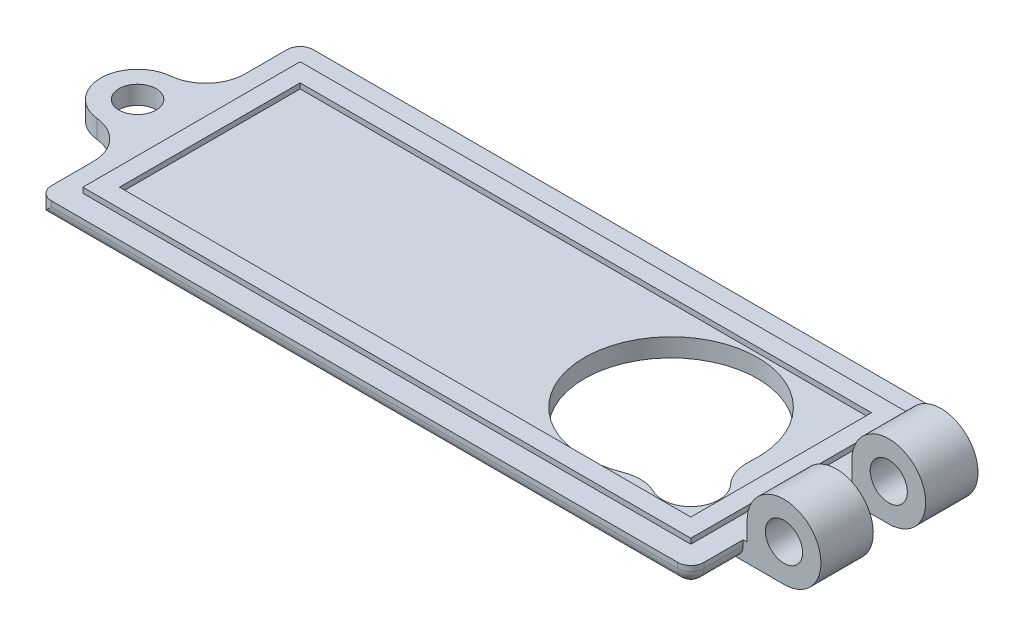
SolidWorks part; units mm, degrees
ref_plane "Front Plane" through (0, 0, 0) normal (0, 0, 1) x (1, 0, 0)
ref_plane "Top Plane" through (0, 0, 0) normal (0, 1, 0) x (1, 0, 0)
ref_plane "Right Plane" through (0, 0, 0) normal (1, 0, 0) x (0, 0, -1)
sketch "Sketch1" plane through (0, 0, 0) normal (0, 1, 0) x (1, 0, 0)
  line L1 (0, 0) -> (63.2968, 0)
  line L2 (0, 0) -> (0, 25.4)
  line L3 (0, 25.4) -> (63.2968, 25.4)
  line L4 (63.2968, 0) -> (63.2968, 25.4)
  dimension "D1" = 25.4
  dimension "D2" = 63.2968
extrude "Boss-Extrude1" add sketch "Sketch1" along normal blind 1.778
sketch "Sketch2" plane through (0, 1.778, 0) normal (0, 1, 0) x (1, 0, 0)
  line L4 (59.3598, 21.463) -> (3.937, 21.463)
  line L5 (3.937, 21.463) -> (3.937, 3.937)
  line L6 (3.937, 3.937) -> (59.3598, 3.937)
  line L7 (59.3598, 3.937) -> (59.3598, 21.463)
  line L8 (2.159, 23.241) -> (2.159, 2.159)
  line L9 (2.159, 2.159) -> (61.1378, 2.159)
  line L10 (61.1378, 2.159) -> (61.1378, 23.241)
  line L11 (61.1378, 23.241) -> (2.159, 23.241)
  line L12 (2.159, 23.241) -> (2.159, 2.159)
  line L13 (2.159, 2.159) -> (61.1378, 2.159)
  line L14 (61.1378, 2.159) -> (61.1378, 23.241)
  line L15 (61.1378, 23.241) -> (2.159, 23.241)
  dimension "D1" = 2.159
  dimension "D2" = 1.778
extrude "Boss-Extrude2" add sketch "Sketch2" along normal blind 0.508
sketch "Sketch3" plane through (0, 0, 0) normal (0, -1, 0) x (1, 0, 0)
  line L0 (63.2968, 0) -> (63.2968, -25.4) construction
  line L1 (63.2968, -25.4) -> (0, -25.4) construction
  line L2 (0, 0) -> (63.2968, 0) construction
  circle A0 centre (48.6791, -12.7) radius 6.6167 construction
  arc A1 (51.7878, -4.9021) -> (57.0454, -12.0103) centre (48.6791, -12.7) ccw
  circle A2 centre (56.0451, -7.2517) radius 1.4605 construction
  arc A3 (58.0479, -9.1076) -> (54.8568, -4.7933) centre (56.0451, -7.2517) ccw
  circle A4 centre (56.0451, -7.2517) radius 2.7305 construction
  circle A5 centre (48.6791, -12.7) radius 8.3947 construction
  arc A6 (58.0479, -9.1076) -> (57.0454, -12.0103) centre (60.8425, -11.6972) ccw
  arc A7 (54.8568, -4.7933) -> (51.7878, -4.9021) centre (53.1988, -1.363) cw
  dimension "D2" = 13.2334
  dimension "D3" = 12.7
  dimension "D5" = 2.921
  dimension "D6" = 7.2517
  dimension "D7" = 7.2517
  dimension "D8" = 1.27
  dimension "D9" = 3.81
  dimension "D1" = 14.6177
  dimension "D4" = 1.778
extrude "Cut-Extrude1" cut sketch "Sketch3" against normal through all
sketch "Sketch4" plane through (0, 0, 0) normal (0, 0, 1) x (1, 0, 0)
  line L2 (67.2592, 3.5814) -> (63.6778, 3.5814) construction
  line L3 (63.2968, 1.778) -> (63.2968, 0) construction
  line L4 (63.6778, 3.5814) -> (63.6778, 1.778)
  line L5 (63.6778, 1.778) -> (63.2968, 1.778)
  line L6 (63.2968, 0) -> (67.2592, 0)
  circle A0 centre (67.2592, 3.5814) radius 1.8034
  arc A1 (67.2592, 0) -> (63.6778, 3.5814) centre (67.2592, 3.5814) ccw
  circle A3 centre (67.2592, 3.5814) radius 3.5814 construction
  point P5 (0, 0)
  line M8 (63.2968, 0) -> (63.2968, 1.778)
  dimension "D2" = 3.6068
  dimension "D3" = 0.381
  dimension "D1" = 1.778
extrude "Boss-Extrude3" add sketch "Sketch4" against normal up to surface (25.4 mm away) contours L6 A1 L4 L5 A0 M8 region at (69.7181, 6.0403, 0) up to face at (31.6484, 0.889, -25.4)
sketch "Sketch5" plane through (0, 1.778, 0) normal (0, 1, 0) x (1, 0, 0)
  line L0 (70.8406, 0) -> (70.8406, 25.4) construction
  line L1 (63.2968, 25.4) -> (70.8406, 25.4)
  line L2 (63.2968, 25.4) -> (63.2968, 20.32)
  line L3 (63.2968, 20.32) -> (70.8406, 20.32)
  line L4 (70.8406, 25.4) -> (70.8406, 20.32)
  line L5 (63.2968, 15.24) -> (63.2968, 10.16)
  line L6 (63.2968, 15.24) -> (70.8406, 15.24)
  line L7 (70.8406, 15.24) -> (70.8406, 10.16)
  line L8 (63.2968, 10.16) -> (70.8406, 10.16)
  line L9 (63.2968, 5.08) -> (63.2968, 0)
  line L10 (63.2968, 5.08) -> (70.8406, 5.08)
  line L11 (70.8406, 5.08) -> (70.8406, 0)
  line L12 (63.2968, 0) -> (70.8406, 0)
  line L13 (63.6778, 0) -> (70.8406, 0) construction
  line L14 (63.6778, 25.4) -> (0, 25.4) construction
  line L15 (63.6778, 25.4) -> (63.6778, 0) construction
  dimension "D2" = 5.08
  dimension "D3" = 0.381
  dimension "D1" = 3
extrude "Cut-Extrude2" cut sketch "Sketch5" against normal through all both and the other way through all
ref_plane "Plane1" through (31.6484, 0, 0) normal (1, 0, 0) x (0, 0, -1)
sketch "Sketch6" plane through (0, 1.778, 0) normal (0, 1, 0) x (1, 0, 0)
  line L0 (0, 25.4) -> (0, 0) construction
  line L1 (0, 16.2814) -> (0, 9.1186)
  line L2 (-3.0734, 16.2814) -> (0, 16.2814)
  line L3 (-3.0734, 9.1186) -> (0, 9.1186)
  line L4 (-3.0734, 12.7) -> (-1.27, 12.7) construction
  circle A0 centre (-3.0734, 12.7) radius 1.8034
  arc A1 (-3.0734, 16.2814) -> (-3.0734, 9.1186) centre (-3.0734, 12.7) ccw
  circle A2 centre (-3.0734, 12.7) radius 3.5814 construction
  point P3 (-4.848, 9.1186)
  point P7 (0, 12.7)
  dimension "D2" = 3.6068
  dimension "D3" = 1.27
  dimension "D1" = 1.778
extrude "Boss-Extrude4" add sketch "Sketch6" against normal up to surface (1.778 mm away) up to face at (54.0681, 0, -12.7)
fillet "Fillet1" radius 3.81 2 edges at (0, 0.889, -9.1186) (0, 0.889, -16.2814)
fillet "Fillet2" radius 1.27 9 edges at (63.2968, 0.889, 0) (63.2968, 0.889, -25.4) (0, 0.889, -25.4) (31.6484, 0, -25.4) (63.2968, 0, -22.86) (63.2968, 0, -12.7) (63.2968, 0, -2.54) (0, 0.889, 0) (31.6484, 0, 0)
